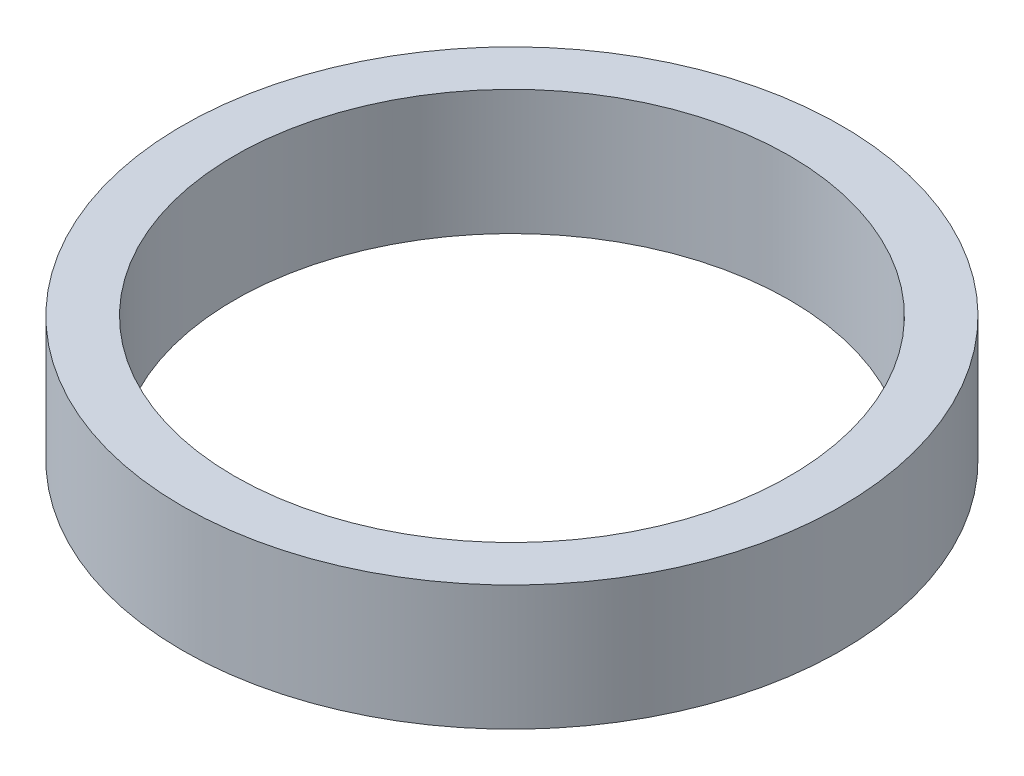
SolidWorks part; units mm, degrees
ref_plane "Front Plane" through (0, 0, 0) normal (0, 0, 1) x (1, 0, 0)
ref_plane "Top Plane" through (0, 0, 0) normal (0, 1, 0) x (1, 0, 0)
ref_plane "Right Plane" through (0, 0, 0) normal (1, 0, 0) x (0, 0, -1)
sketch "Sketch1" plane through (0, 0, 0) normal (0, 1, 0) x (1, 0, 0)
  circle A0 centre (0, 0) radius 47.5
  dimension "FLANGE_OD" = 95
extrude "Boss-Extrude1" add sketch "Sketch1" along normal blind 18
sketch "Sketch2" plane through (0, 0, 0) normal (0, 1, 0) x (1, 0, 0)
  circle A0 centre (0, 0) radius 40
  dimension "BORE_D" = 80
extrude "Cut-Extrude1" cut sketch "Sketch2" along normal through all
sketch "Sketch3" plane through (0, 18, 0) normal (0, 1, 0) x (1, 0, 0)
  circle A0 centre (0, 0) radius 22.2107 construction
  circle A1 centre (-22.2107, 0) radius 1.5
  dimension "BOLT_D" = 3
  dimension "BOLT_PCD" = 44.4215
extrude "Cut-Extrude2" cut sketch "Sketch3" against normal blind 17.4404 rebuild error yes
pattern_circular "CirPattern1" count 5 over 360 rebuild error yes
